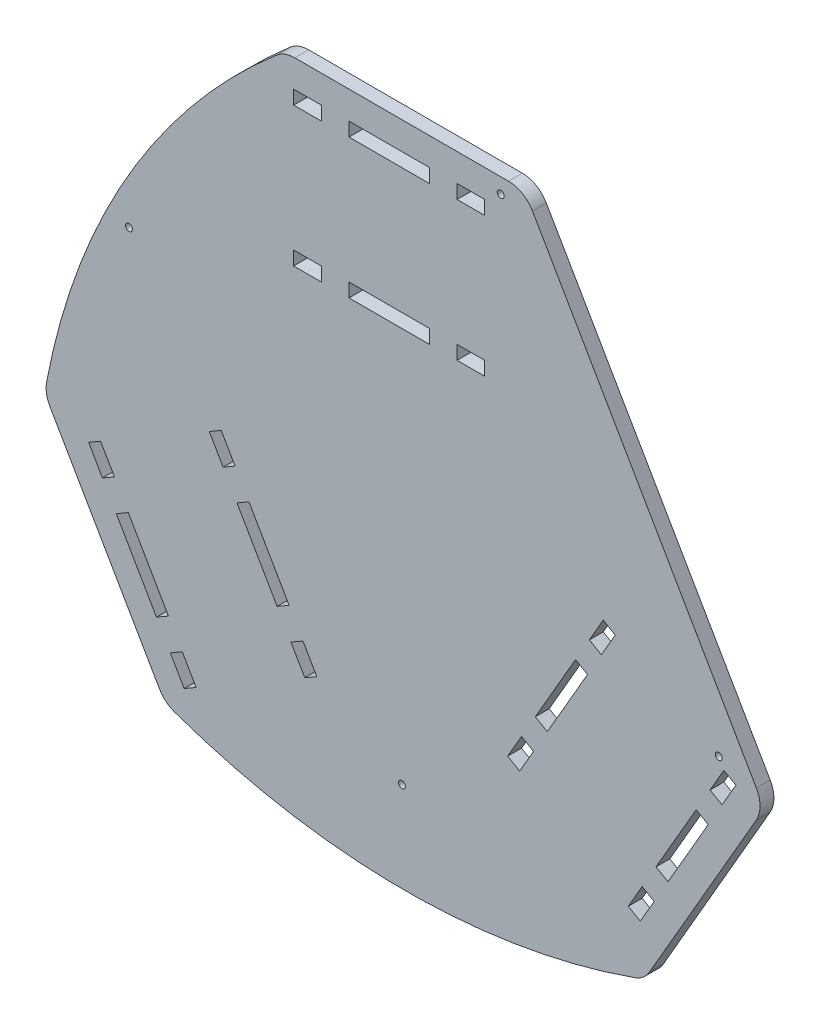
SolidWorks part; units mm, degrees
ref_plane "Front Plane" through (0, 0, 0) normal (0, 0, 1) x (1, 0, 0)
ref_plane "Top Plane" through (0, 0, 0) normal (0, 1, 0) x (1, 0, 0)
ref_plane "Right Plane" through (0, 0, 0) normal (1, 0, 0) x (0, 0, -1)
sketch "Sketch1" plane through (0, 0, 0) normal (0, 0, 1) x (0.866, -0.5, 0)
  line L0 (125, -43.3013) -> (125, 43.3013)
  line L1 (-100, 86.6025) -> (-100, -86.6025)
  line L2 (-25, -129.9038) -> (125, -43.3013)
  line L3 (125, 43.3013) -> (-25, 129.9038)
  line L4 (-25, 129.9038) -> (-100, 86.6025)
  line L5 (-100, -86.6025) -> (-25, -129.9038)
  circle A0 centre (0, 0) radius 100 construction
  dimension "D1" = 200
  dimension "D2" = 225
  dimension "D3" = 3
extrude "Boss-Extrude1" add sketch "Sketch1" along normal blind 5
sketch "Sketch2" plane through (0, 0, 5) normal (0, 0, 1) x (1, 0, 0)
  line L0 (13.45, 112.5) -> (19.95, 112.5) construction
  line L1 (-25, 107.5) -> (25, 107.5)
  line L2 (-25, 107.5) -> (-25, 67.5)
  line L3 (-25, 67.5) -> (25, 67.5)
  line L4 (25, 107.5) -> (25, 67.5)
  line L5 (-40.05, 115) -> (-35.05, 115)
  line L6 (-40.05, 115) -> (-40.05, 110)
  line L7 (-40.05, 110) -> (-35.05, 110)
  line L8 (-35.05, 115) -> (-35.05, 110)
  line L9 (-24.55, 115) -> (-19.55, 115)
  line L10 (-24.55, 112.5) -> (-31.05, 112.5) construction
  line L14 (-24.55, 62.1999) -> (-31.05, 62.1999) construction
  line L15 (-24.55, 115) -> (-24.55, 110)
  line L16 (-24.55, 110) -> (-19.55, 110)
  line L17 (-19.55, 115) -> (-19.55, 110)
  line L18 (-14.55, 115) -> (13.45, 115)
  line L19 (-14.55, 115) -> (-14.55, 110)
  line L24 (-14.55, 110) -> (13.45, 110)
  line L25 (13.45, 115) -> (13.45, 110)
  line L26 (-40.05, 64.6999) -> (-35.05, 64.6999)
  line L27 (-40.05, 64.6999) -> (-40.05, 59.6999)
  line L28 (-40.05, 59.6999) -> (-35.05, 59.6999)
  line L29 (129.9038, -25) -> (43.3013, 125) construction
  line L30 (-43.3013, 125) -> (-129.9038, -25) construction
  line L31 (-86.6025, -100) -> (86.6025, -100) construction
  line L32 (25, 107.5) -> (-25, 67.5) construction
  line L33 (0, 87.5) -> (0, 0) construction
  line L49 (-35.05, 64.6999) -> (-35.05, 59.6999)
  line L50 (-24.55, 64.6999) -> (-19.55, 64.6999)
  line L51 (-24.55, 64.6999) -> (-24.55, 59.6999)
  line L52 (-24.55, 59.6999) -> (-19.55, 59.6999)
  line L53 (-19.55, 64.6999) -> (-19.55, 59.6999)
  line L54 (-14.55, 64.6999) -> (13.45, 64.6999)
  line L55 (-14.55, 64.6999) -> (-14.55, 59.6999)
  line L56 (-14.55, 59.6999) -> (13.45, 59.6999)
  line L57 (13.45, 64.6999) -> (13.45, 59.6999)
  line L58 (13.45, 62.1999) -> (19.95, 62.1999) construction
  line L117 (-19.55, 115) -> (-19.55, 110) construction
  line L118 (-19.55, 110) -> (-24.55, 110) construction
  line L120 (-14.55, 115) -> (-14.55, 110) construction
  line L121 (13.45, 115) -> (-14.55, 115) construction
  line L123 (28.95, 110) -> (23.95, 110)
  line L124 (28.95, 110) -> (28.95, 115)
  line L125 (28.95, 115) -> (23.95, 115)
  line L126 (23.95, 110) -> (23.95, 115)
  line L127 (28.95, 59.6999) -> (23.95, 59.6999)
  line L128 (28.95, 59.6999) -> (28.95, 64.6999)
  line L129 (28.95, 64.6999) -> (23.95, 64.6999)
  line L130 (23.95, 59.6999) -> (23.95, 64.6999)
  circle A0 centre (-31.05, 112.5) radius 1.5
  circle A1 centre (-31.05, 62.1999) radius 1.5
  circle A2 centre (0, 0) radius 100 construction
  circle A3 centre (19.95, 112.5) radius 1.5
  circle A4 centre (19.95, 62.1999) radius 1.5
  dimension "D5" = 3
  dimension "D1" = 87.5
  dimension "D3" = 40
  dimension "D4" = 50
  dimension "D6" = 6.5
sketch "Sketch3" plane through (0, 0, 5) normal (0, 0, 1) x (1, 0, 0)
  line L12 (-86.6025, -100) -> (86.6025, -100)
  line L13 (86.6025, -100) -> (129.9038, -25)
  line L14 (129.9038, -25) -> (43.3013, 125)
  line L15 (43.3013, 125) -> (-43.3013, 125)
  line L16 (-43.3013, 125) -> (-129.9038, -25)
  line L17 (-129.9038, -25) -> (-86.6025, -100)
  line L18 (-86.6025, -100) -> (86.6025, -100)
  line L19 (86.6025, -100) -> (129.9038, -25)
  line L20 (129.9038, -25) -> (43.3013, 125)
  line L21 (43.3013, 125) -> (-43.3013, 125)
  line L22 (-43.3013, 125) -> (-129.9038, -25)
  line L23 (-129.9038, -25) -> (-86.6025, -100)
  dimension "D1" = 0
extrude "Boss-Extrude2" add sketch "Sketch3" against normal blind 5
sketch "Sketch4" plane through (0, 0, 5) normal (0, 0, 1) x (1, 0, 0)
  line L0 (-30.05, 110) -> (-30.05, 115) construction
  line L1 (-40.05, 110) -> (-30.05, 110)
  line L2 (-40.05, 110) -> (-40.05, 115)
  line L3 (-40.05, 115) -> (-30.05, 115)
  line L4 (28.95, 110) -> (28.95, 115)
  line L5 (18.95, 115) -> (28.95, 115)
  line L6 (-30.05, 115) -> (-30.05, 110)
  line L7 (18.95, 110) -> (28.95, 110)
  line L8 (-20.05, 115) -> (-20.05, 110)
  line L9 (-40.05, 59.6999) -> (-30.05, 59.6999)
  line L10 (8.95, 115) -> (8.95, 110)
  line L12 (18.95, 115) -> (18.95, 110)
  line L13 (-20.05, 110) -> (-20.05, 115) construction
  line L14 (8.95, 110) -> (8.95, 115) construction
  line L15 (18.95, 110) -> (18.95, 115) construction
  line L16 (-20.05, 115) -> (8.95, 115)
  line L17 (-20.05, 110) -> (8.95, 110)
  line L18 (-40.05, 59.6999) -> (-40.05, 64.6999)
  line L19 (-40.05, 64.6999) -> (-30.05, 64.6999)
  line L20 (28.95, 59.6999) -> (28.95, 64.6999)
  line L21 (18.95, 64.6999) -> (28.95, 64.6999)
  line L22 (-30.05, 64.6999) -> (-30.05, 59.6999)
  line L23 (18.95, 59.6999) -> (28.95, 59.6999)
  line L24 (-20.05, 64.6999) -> (-20.05, 59.6999)
  line L25 (8.95, 64.6999) -> (8.95, 59.6999)
  line L26 (18.95, 64.6999) -> (18.95, 59.6999)
  line L27 (-20.05, 64.6999) -> (8.95, 64.6999)
  line L28 (-20.05, 59.6999) -> (8.95, 59.6999)
  line L29 (115.2878, -20.3157) -> (110.2878, -28.9759)
  line L30 (115.2878, -20.3157) -> (119.6179, -22.8157)
  line L31 (119.6179, -22.8157) -> (114.6179, -31.4759)
  line L32 (80.7878, -80.0714) -> (85.1179, -82.5714)
  line L33 (90.1179, -73.9112) -> (85.1179, -82.5714)
  line L34 (114.6179, -31.4759) -> (110.2878, -28.9759)
  line L35 (85.7878, -71.4112) -> (80.7878, -80.0714)
  line L36 (109.6179, -40.1362) -> (105.2878, -37.6362)
  line L37 (71.7267, 4.8343) -> (66.7267, -3.8259)
  line L38 (95.1179, -65.2509) -> (90.7878, -62.7509)
  line L39 (90.1179, -73.9112) -> (85.7878, -71.4112)
  line L40 (109.6179, -40.1362) -> (95.1179, -65.2509)
  line L41 (105.2878, -37.6362) -> (90.7878, -62.7509)
  line L42 (71.7267, 4.8343) -> (76.0568, 2.3343)
  line L43 (76.0568, 2.3343) -> (71.0568, -6.3259)
  line L44 (37.2267, -54.9214) -> (41.5568, -57.4214)
  line L45 (46.5568, -48.7612) -> (41.5568, -57.4214)
  line L46 (71.0568, -6.3259) -> (66.7267, -3.8259)
  line L47 (42.2267, -46.2612) -> (37.2267, -54.9214)
  line L48 (66.0568, -14.9862) -> (61.7267, -12.4862)
  line L49 (51.5568, -40.1009) -> (47.2267, -37.6009)
  line L50 (46.5568, -48.7612) -> (42.2267, -46.2612)
  line L51 (66.0568, -14.9862) -> (51.5568, -40.1009)
  line L52 (61.7267, -12.4862) -> (47.2267, -37.6009)
  line L53 (-75.2378, -89.6843) -> (-80.2378, -81.0241)
  line L54 (-75.2378, -89.6843) -> (-79.5679, -92.1843)
  line L55 (-79.5679, -92.1843) -> (-84.5679, -83.5241)
  line L56 (-109.7378, -29.9286) -> (-114.0679, -32.4286)
  line L57 (-109.0679, -41.0888) -> (-114.0679, -32.4286)
  line L58 (-84.5679, -83.5241) -> (-80.2378, -81.0241)
  line L59 (-104.7378, -38.5888) -> (-109.7378, -29.9286)
  line L60 (-89.5679, -74.8638) -> (-85.2378, -72.3638)
  line L61 (-31.6767, -64.5343) -> (-36.6767, -55.874)
  line L62 (-104.0679, -49.7491) -> (-99.7378, -47.2491)
  line L63 (-109.0679, -41.0888) -> (-104.7378, -38.5888)
  line L64 (-89.5679, -74.8638) -> (-104.0679, -49.7491)
  line L65 (-85.2378, -72.3638) -> (-99.7378, -47.2491)
  line L66 (-31.6767, -64.5343) -> (-36.0068, -67.0343)
  line L67 (-36.0068, -67.0343) -> (-41.0068, -58.374)
  line L68 (-66.1767, -4.7785) -> (-70.5068, -7.2785)
  line L69 (-65.5068, -15.9388) -> (-70.5068, -7.2785)
  line L70 (-41.0068, -58.374) -> (-36.6767, -55.874)
  line L71 (-61.1767, -13.4388) -> (-66.1767, -4.7785)
  line L72 (-46.0068, -49.7138) -> (-41.6767, -47.2138)
  line L73 (-60.5068, -24.599) -> (-56.1767, -22.099)
  line L74 (-65.5068, -15.9388) -> (-61.1767, -13.4388)
  line L75 (-46.0068, -49.7138) -> (-60.5068, -24.599)
  line L76 (-41.6767, -47.2138) -> (-56.1767, -22.099)
  line L77 (18.95, 64.6999) -> (8.95, 64.6999) construction
  line L78 (18.95, 59.6999) -> (18.95, 64.6999) construction
  line L79 (42.2267, -46.2612) -> (46.5568, -48.7612) construction
  line L80 (42.2267, -46.2612) -> (47.2267, -37.6009) construction
  circle A0 centre (0.4282, 0.0852) radius 100 construction
  dimension "D1" = 2
  dimension "D2" = 3
extrude "Cut-Extrude2" cut sketch "Sketch4" against normal blind 5
sketch "Sketch5" plane through (0, 0, 5) normal (0, 0, 1) x (1, 0, 0)
  line L0 (-129.9038, -25) -> (-43.3013, 125)
  line L1 (-43.3013, 125) -> (-41.9709, 125.5807)
  line L2 (86.6025, -100) -> (-86.6025, -100)
  line L3 (-86.6025, -100) -> (-86.5891, -98.5285)
  arc A0 (-129.9038, -25) -> (-43.3013, 125) centre (116.4984, -67.2604) cw
  arc A1 (86.6025, -100) -> (-86.6025, -100) centre (0, 134.5208) cw
  dimension "D1" = 250
extrude "Boss-Extrude3" add sketch "Sketch5" against normal blind 5 contours A0 L0 | A1 L2 region at (-91.9792, 53.1042, 5) region at (0, -106.2084, 5)
sketch "Sketch7" plane through (0, 0, 5) normal (0, 0, 1) x (1, 0, 0)
  line L0 (129.9038, -25) -> (43.3013, 125) construction
  line L1 (-99.4749, 42.0456) -> (34.7071, 119.5156) construction
  line L2 (-99.4749, 42.0456) -> (-20.7349, -94.3361) construction
  line L3 (-20.7349, -94.3361) -> (113.4471, -16.8661) construction
  line L4 (34.7071, 119.5156) -> (113.4471, -16.8661) construction
  circle A0 centre (-99.4749, 42.0456) radius 1.25
  circle A1 centre (34.7071, 119.5156) radius 1.25
  circle A2 centre (113.4471, -16.8661) radius 1.25
  circle A3 centre (34.7071, 119.5156) radius 1.98 construction
  circle A4 centre (113.4471, -16.8661) radius 1.98 construction
  circle A5 centre (-99.4749, 42.0456) radius 1.98 construction
  circle A6 centre (-0.9376, -82.9061) radius 1.25
  dimension "D1" = 2.5
extrude "Cut-Extrude4" cut sketch "Sketch7" against normal blind 5
extrude "Cut-Extrude5" [suppressed] cut sketch "Sketch2" against normal blind 10
fillet "Fillet1" [suppressed] radius 5
ref_axis "Axis1" [suppressed] through (0, 0, 0) along (0, 0, -1)
pattern_circular "CirPattern1" [suppressed] count 3 over 360 about axis through (0, 0, 0) along (0, 0, -1) of bodies 108
fillet "Fillet2" radius 10 6 edges at (129.9038, -25, 2.5) (86.6025, -100, 2.5) (-86.6025, -100, 2.5) (-129.9038, -25, 2.5) (-43.3013, 125, 2.5) (43.3013, 125, 2.5)
